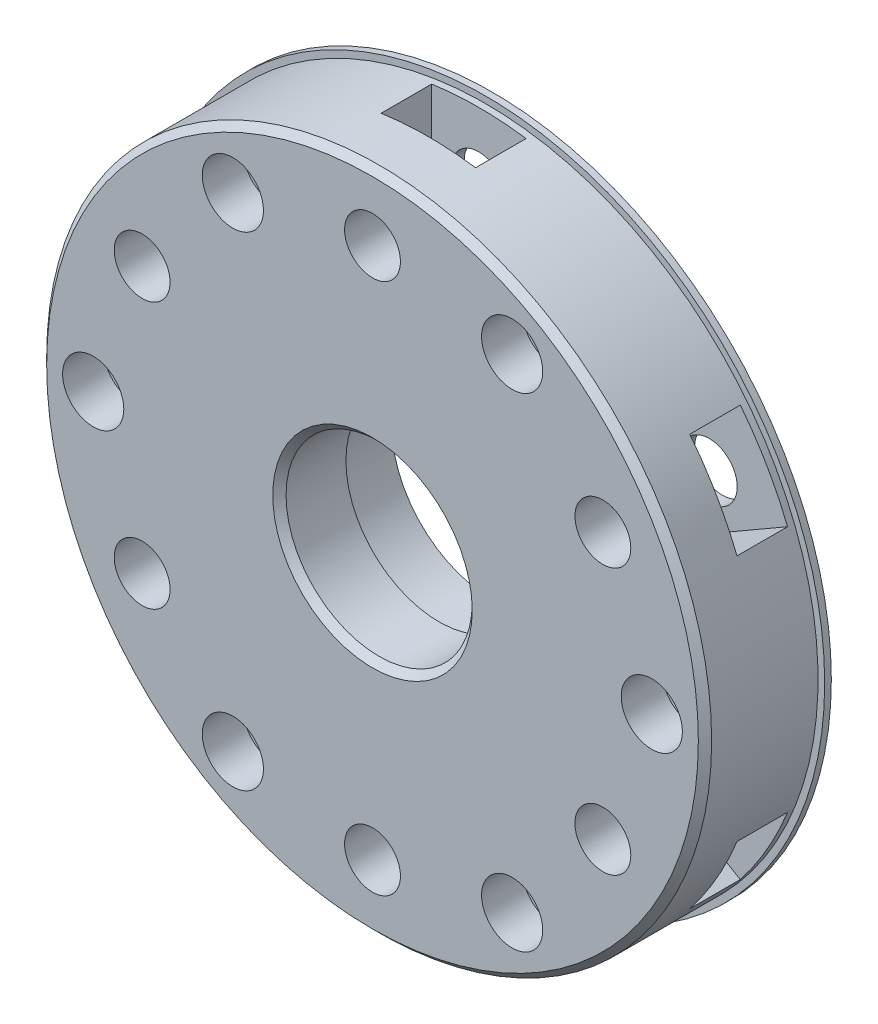
SolidWorks part; units mm, degrees
material "ABS"
ref_plane "Front Plane" through (0, 0, 0) normal (0, 0, 1) x (1, 0, 0)
ref_plane "Top Plane" through (0, 0, 0) normal (0, 1, 0) x (1, 0, 0)
ref_plane "Right Plane" through (0, 0, 0) normal (1, 0, 0) x (0, 0, -1)
sketch "Output Master Sketch" plane through (0, 0, 0) normal (0, 0, 1) x (1, 0, 0)
  circle A0 centre (0, 0) radius 21 construction
  circle A1 centre (21, 0) radius 3.05 construction
  circle A2 centre (10.5, -18.1865) radius 3.05 construction
  circle A3 centre (-10.5, -18.1865) radius 3.05 construction
  circle A4 centre (-21, 0) radius 3.05 construction
  circle A5 centre (-10.5, 18.1865) radius 3.05 construction
  circle A6 centre (10.5, 18.1865) radius 3.05 construction
  circle A7 centre (0, 0) radius 25
  point P17 (0, 0)
extrude "Boss-Extrude1" add sketch "Output Master Sketch" along normal blind 9
sketch "Sketch4" plane through (0, 0, 0) normal (0, 0, 1) x (1, 0, 0)
  circle A0 centre (21, 0) radius 3.05
  circle A1 centre (21, 0) radius 3.05 construction
  circle A2 centre (10.5, -18.1865) radius 3.05
  circle A3 centre (-10.5, -18.1865) radius 3.05
  circle A4 centre (-21, 0) radius 3.05
  circle A5 centre (-10.5, 18.1865) radius 3.05
  circle A6 centre (10.5, 18.1865) radius 3.05
  point P17 (0, 0)
  dimension "D1" = 6
extrude "Cut-Extrude1" cut sketch "Sketch4" along normal blind 4
sketch "Sketch5" plane through (0, 0, 0) normal (0, 0, -1) x (-1, 0, 0)
  circle A0 centre (0, 0) radius 25
  circle A1 centre (0, 0) radius 25.5
  circle A2 centre (0, 0) radius 25 construction
  dimension "D1" = 0.5
extrude "Boss-Extrude2" add sketch "Sketch5" against normal blind 0.5
sketch "Sketch6" plane through (0, 0, 0) normal (0, 0, -1) x (-1, 0, 0)
  circle A0 centre (-21, 0) radius 1.55
  circle A1 centre (-10.5, 18.1865) radius 1.55
  circle A2 centre (10.5, 18.1865) radius 1.55
  circle A3 centre (21, 0) radius 1.55
  circle A4 centre (10.5, -18.1865) radius 1.55
  circle A5 centre (-10.5, -18.1865) radius 1.55
  point P15 (0, 0)
  dimension "D1" = 3.1
  dimension "D2" = 6
extrude "Cut-Extrude2" cut sketch "Sketch6" against normal through all
sketch "Sketch7" plane through (0, 0, 9) normal (0, 0, 1) x (1, 0, 0)
  circle A0 centre (-21, 0) radius 2.3
  circle A1 centre (-10.5, 18.1865) radius 2.3
  circle A2 centre (10.5, 18.1865) radius 2.3
  circle A3 centre (21, 0) radius 2.3
  circle A4 centre (10.5, -18.1865) radius 2.3
  circle A5 centre (-10.5, -18.1865) radius 2.3
  point P16 (0, 0)
  dimension "D1" = 4.6
  dimension "D2" = 6
extrude "Cut-Extrude3" cut sketch "Sketch7" against normal blind 3.1
chamfer "Chamfer1" distance 0.5 angle 45 1 edges at (25, 0, 9)
sketch "Sketch8" plane through (0, 0, 0) normal (0, 0, -1) x (-1, 0, 0)
  circle A0 centre (0, 0) radius 7
  dimension "D1" = 14
extrude "Cut-Extrude4" cut sketch "Sketch8" against normal blind 10
sketch "Sketch9" plane through (0, 0, 0) normal (0, 0, -1) x (-1, 0, 0)
  circle A0 centre (0, 0) radius 7.55
  dimension "D1" = 15.1
extrude "Cut-Extrude5" cut sketch "Sketch9" against normal blind 4
sketch "Sketch10" plane through (0, 0, 9) normal (0, 0, 1) x (1, 0, 0)
  line L1 (0, 20) -> (-17.3205, 10) construction
  line L2 (-17.3205, 10) -> (-17.3205, -10) construction
  line L3 (-17.3205, -10) -> (0, -20) construction
  line L4 (0, -20) -> (17.3205, -10) construction
  line L5 (17.3205, -10) -> (17.3205, 10) construction
  line L6 (17.3205, 10) -> (0, 20) construction
  circle A0 centre (0, 0) radius 20 construction
  circle A1 centre (0, 20) radius 2.1
  circle A2 centre (17.3205, 10) radius 2.1
  circle A3 centre (17.3205, -10) radius 2.1
  circle A4 centre (0, -20) radius 2.1
  circle A5 centre (-17.3205, -10) radius 2.1
  circle A6 centre (-17.3205, 10) radius 2.1
  point P22 (0, 0)
  dimension "D1" = 40
  dimension "D2" = 4.2
  dimension "D3" = 6
extrude "M4 Thru" cut sketch "Sketch10" against normal through all
chamfer "Chamfer3" distance 0.5 angle 45 1 edges at (7, 0, 9)
sketch "Sketch11" plane through (0, 0, 9) normal (0, 0, 1) x (1, 0, 0)
  line L1 (0, 24.0992) -> (-3.55, 22.0496)
  line L2 (-3.55, 22.0496) -> (-3.55, 17.9504)
  line L3 (-3.55, 17.9504) -> (0, 15.9008)
  line L4 (0, 15.9008) -> (3.55, 17.9504)
  line L5 (3.55, 17.9504) -> (3.55, 22.0496)
  line L6 (3.55, 22.0496) -> (0, 24.0992)
  circle A0 centre (0, 20) radius 3.55 construction
  dimension "D1" = 7.1
extrude "M4 Hexnut Cut" cut sketch "Sketch11" along normal blind 3.8 from offset 8 offset against normal yes
ref_plane "Plane2" through (0, 22.0496, 0) normal (0, 1, 0) x (1, 0, 0)
sketch "Sketch12" plane through (0, 22.0496, 0) normal (0, 1, 0) x (1, 0, 0)
  line L1 (-3.55, -1) -> (3.55, -1)
  line L2 (-3.55, -1) -> (-3.55, -4.8)
  line L3 (-3.55, -4.8) -> (3.55, -4.8)
  line L4 (3.55, -1) -> (3.55, -4.8)
extrude "M4 Hexnut Slot" cut sketch "Sketch12" along normal through all contours L2 L1 L4 L3
pattern_circular "M4 Hexnut Pattern" count 6 over 360 about axis through (0, 0, 10) along (0, 0, -1) of "M4 Hexnut Cut", "M4 Hexnut Slot" reverse direction yes
